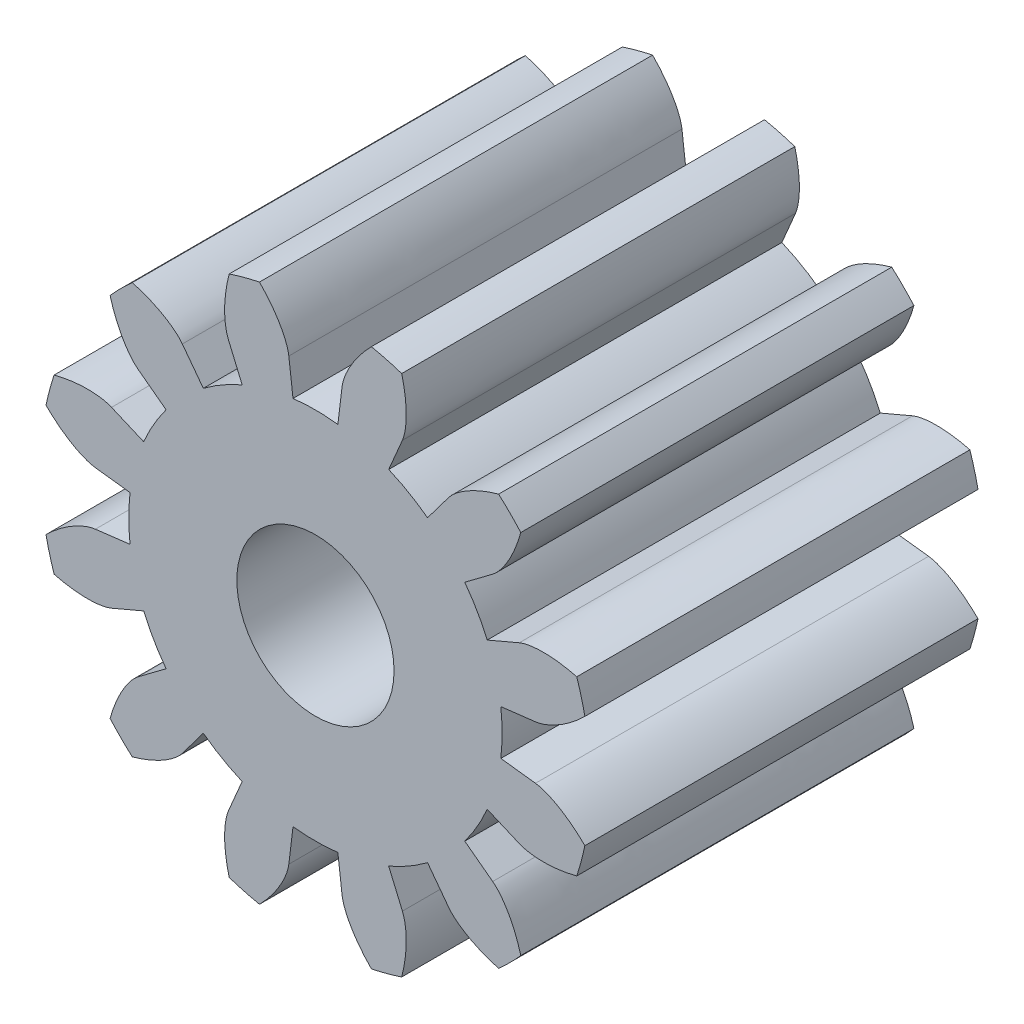
SolidWorks part; units mm, degrees
ref_plane "前视基准面" through (0, 0, 0) normal (0, 0, 1) x (1, 0, 0)
ref_plane "上视基准面" through (0, 0, 0) normal (0, 1, 0) x (1, 0, 0)
ref_plane "右视基准面" through (0, 0, 0) normal (1, 0, 0) x (0, 0, -1)
other "Configuration Table"
sketch "草图1" plane through (0, 0, 0) normal (0, 0, 1) x (1, 0, 0)
  line L0 (0, 0) -> (3, 0) construction
  line L1 (0, 0) -> (2.9743, 0.3916) construction
  line L2 (0, 0) -> (2.7987, 0.3386)
  line L3 (2.9743, 0.3916) -> (2.9743, -0.3916) construction
  line L4 (0, 0) -> (2.7987, -0.3386)
  circle A0 centre (0, 0) radius 3.5
  circle A1 centre (0, 0) radius 3 construction
  circle A2 centre (0, 0) radius 2.375
  circle A3 centre (0, 0) radius 2.8191 construction
  circle A4 centre (0, 0) radius 1
  spline S0 degree 4 poles (2.7987, 0.3386) (2.82, 0.3411) (2.879, 0.3528) (2.9873, 0.3924) (3.1523, 0.4801) (3.3463, 0.6259) (3.5662, 0.8464) (3.7825, 1.1408) (3.9711, 1.4947) (4.1197, 1.9006) (4.217, 2.3214) (4.2662, 2.7504) (4.2704, 3.2034) (4.2171, 3.7619) (4.0685, 4.4153) (3.7871, 5.1414) (3.3531, 5.89) (2.817, 6.5681) (2.1934, 7.1673) (1.5005, 7.6821) (0.7472, 8.1086) (-0.0448, 8.4455) (-0.8785, 8.6913) (-1.6117, 8.8286) (-2.2718, 8.8897) (-2.746, 8.9054) (-3.1682, 8.8973) (-3.4474, 8.8817) (-3.8403, 8.8483) (-4.1356, 8.8059) (-4.4307, 8.7603) (-4.5782, 8.7282) (-4.6735, 8.7099) knots 0 0 0 0 0 0.005604 0.015718 0.02996 0.048734 0.068727 0.096889 0.125051 0.153212 0.181374 0.209535 0.237696 0.271429 0.327752 0.384075 0.440398 0.496721 0.553044 0.609367 0.66569 0.722013 0.778336 0.834659 0.86282 0.890982 0.909091 0.931818 0.954545 0.977273 1 1 1 1 1 construction
  spline S1 degree 4 poles (2.7987, 0.3386) (2.82, 0.3411) (2.879, 0.3528) (2.9873, 0.3924) (3.1523, 0.4801) (3.3463, 0.6259) (3.5662, 0.8464) (3.7825, 1.1408) (3.9711, 1.4947) (4.1197, 1.9006) (4.217, 2.3214) (4.2662, 2.7504) (4.2704, 3.2034) (4.2171, 3.7619) (4.0685, 4.4153) (3.7871, 5.1414) (3.3531, 5.89) (2.817, 6.5681) (2.1934, 7.1673) (1.5005, 7.6821) (0.7472, 8.1086) (-0.0448, 8.4455) (-0.8785, 8.6913) (-1.6117, 8.8286) (-2.2718, 8.8897) (-2.746, 8.9054) (-3.0694, 8.8992) (-3.2301, 8.8926) (-3.293, 8.8894) knots 0 0 0 0 0 0.005604 0.015718 0.02996 0.048734 0.068727 0.096889 0.125051 0.153212 0.181374 0.209535 0.237696 0.271429 0.327752 0.384075 0.440398 0.496721 0.553044 0.609367 0.66569 0.722013 0.778336 0.834659 0.86282 0.890982 0.909091 0.909091 0.909091 0.909091 0.909091
  spline S2 degree 4 poles (2.7987, -0.3386) (2.82, -0.3411) (2.879, -0.3528) (2.9873, -0.3924) (3.1523, -0.4801) (3.3463, -0.6259) (3.5662, -0.8464) (3.7825, -1.1408) (3.9711, -1.4947) (4.1197, -1.9006) (4.217, -2.3214) (4.2662, -2.7504) (4.2704, -3.2034) (4.2171, -3.7619) (4.0685, -4.4153) (3.7871, -5.1414) (3.3531, -5.89) (2.817, -6.5681) (2.1934, -7.1673) (1.5005, -7.6821) (0.7472, -8.1086) (-0.0448, -8.4455) (-0.8785, -8.6913) (-1.6117, -8.8286) (-2.2718, -8.8897) (-2.746, -8.9054) (-3.1682, -8.8973) (-3.4474, -8.8817) (-3.8403, -8.8483) (-4.1356, -8.8059) (-4.4307, -8.7603) (-4.5782, -8.7282) (-4.6735, -8.7099) knots 0 0 0 0 0 0.005604 0.015718 0.02996 0.048734 0.068727 0.096889 0.125051 0.153212 0.181374 0.209535 0.237696 0.271429 0.327752 0.384075 0.440398 0.496721 0.553044 0.609367 0.66569 0.722013 0.778336 0.834659 0.86282 0.890982 0.909091 0.931818 0.954545 0.977273 1 1 1 1 1 construction
  spline S3 degree 4 poles (2.7987, -0.3386) (2.82, -0.3411) (2.879, -0.3528) (2.9873, -0.3924) (3.1523, -0.4801) (3.3463, -0.6259) (3.5662, -0.8464) (3.7825, -1.1408) (3.9711, -1.4947) (4.1197, -1.9006) (4.217, -2.3214) (4.2662, -2.7504) (4.2704, -3.2034) (4.2171, -3.7619) (4.0685, -4.4153) (3.7871, -5.1414) (3.3531, -5.89) (2.817, -6.5681) (2.1934, -7.1673) (1.5005, -7.6821) (0.7472, -8.1086) (-0.0448, -8.4455) (-0.8785, -8.6913) (-1.6117, -8.8286) (-2.2718, -8.8897) (-2.746, -8.9054) (-3.0694, -8.8992) (-3.2301, -8.8926) (-3.293, -8.8894) knots 0 0 0 0 0 0.005604 0.015718 0.02996 0.048734 0.068727 0.096889 0.125051 0.153212 0.181374 0.209535 0.237696 0.271429 0.327752 0.384075 0.440398 0.496721 0.553044 0.609367 0.66569 0.722013 0.778336 0.834659 0.86282 0.890982 0.909091 0.909091 0.909091 0.909091 0.909091
  point P15 (2.9743, 0)
  dimension "齿顶圆直径" = 7
  dimension "分度圆直径" = 6
  dimension "齿根圆直径" = 4.75
  dimension "基圆直径" = 5.6382
  dimension "内孔直径" = 2
  dimension "渐近线镜像线夹角" = 7.5
extrude "凸台-拉伸1" add sketch "草图1" along normal blind 5 contours A0 | A4
extrude "切除-拉伸1" cut sketch "草图1<3>" along normal through all contours A2 S3 A0 S1 region at (3.0158, 0, 0)
sketch "草图1<3>" plane through (0, 0, 0) normal (0, 0, 1) x (1, 0, 0) same geometry as "草图1"
pattern_circular "阵列(圆周)1" count 12 every 30 about axis through (0, 0, 5) along (0, 0, 1) of "切除-拉伸1"
equation "\"m\" = 0.5'模数"
equation "\"z\"= 12'齿数"
equation "\"a\"= 20度'压力角"
equation "\"d\"= \"m\" * \"z\"'分度圆直径"
equation "\"da\"= ( \"z\" + 2 ) * \"m\"'齿顶圆直径"
equation "\"df\"= ( \"z\" - 2.5 ) * \"m\"'齿根圆直径"
equation "\"s\"= 0.5 * PI * \"m\"'分度圆齿厚"
equation "\"r\"= 0.38 * \"m\"'齿根圆角"
equation "\"B\"= 0.3 * \"d\"'齿厚"
equation "\"db\"= \"m\" * \"z\" * cos ( \"a\" )'基圆直径"
equation "\"rb\"= \"db\" / 2'基圆半径"
equation "\"齿顶圆直径@草图1\"= \"da\""
equation "\"分度圆直径@草图1\"= \"d\""
equation "\"齿根圆直径@草图1\"= \"df\""
equation "\"基圆直径@草图1\"= \"db\""
equation "\"渐近线镜像线夹角@草图1\"= 360 / 4 / \"z\""
equation "\"h\" = 5'齿轮厚度"
equation "\"ir\"= 2'内孔直径"
equation "\"内孔直径@草图1\"= \"ir\""
equation "\"齿轮厚@凸台-拉伸1\"= \"h\""
equation "\"齿轮夹角@阵列(圆周)1\"= 360 / \"z\""
equation "\"齿数@阵列(圆周)1\"= \"z\""
